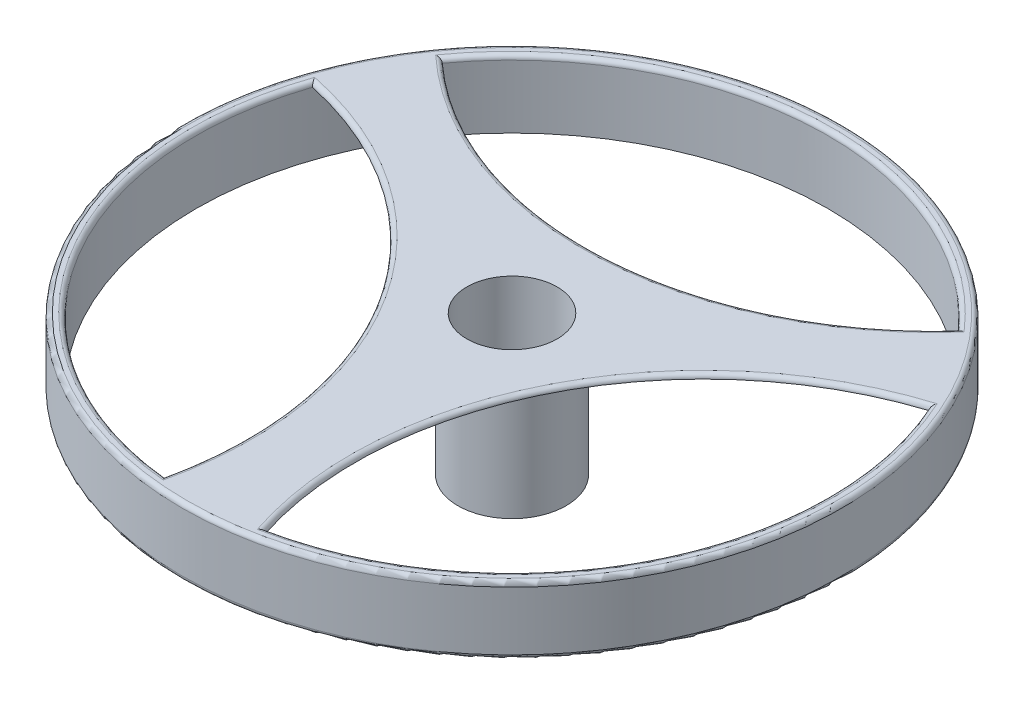
SolidWorks part; units mm, degrees
ref_plane "Front Plane" through (0, 0, 0) normal (0, 0, 1) x (1, 0, 0)
ref_plane "Top Plane" through (0, 0, 0) normal (0, 1, 0) x (1, 0, 0)
ref_plane "Right Plane" through (0, 0, 0) normal (1, 0, 0) x (0, 0, -1)
sketch "Sketch1" plane through (0, 0, 0) normal (0, 1, 0) x (1, 0, 0)
  circle A0 centre (0, 0) radius 7.3
  dimension "D1" = 14.6
extrude "Boss-Extrude1" add sketch "Sketch1" along normal blind 1.5
sketch "Sketch2" plane through (0, 1.5, 0) normal (0, 1, 0) x (1, 0, 0)
  circle A0 centre (0, 0) radius 1.1836 construction
  arc A1 (1.3984, -6.8589) -> (6.3958, 2.845) centre (0, 0) ccw
  arc A2 (1.3984, -6.8589) -> (6.3958, 2.845) centre (8.749, -4.5056) cw
  dimension "D1" = 14
extrude "Cut-Extrude1" cut sketch "Sketch2" against normal blind 1.5
pattern_circular "CirPattern1" count 3 over 360 about axis through (0, 1.5, 0) along (0, -1, 0) of "Cut-Extrude1"
sketch "Sketch3" plane through (0, 1.5, 0) normal (0, 1, 0) x (1, 0, 0)
  circle A0 centre (0, 0) radius 1
  dimension "D1" = 2
extrude "Cut-Extrude2" cut sketch "Sketch3" against normal blind 1.5
sketch "Sketch4" plane through (0, 0, 0) normal (0, -1, 0) x (1, 0, 0)
  circle A0 centre (0, 0) radius 7
extrude "Cut-Extrude3" cut sketch "Sketch4" against normal blind 1.4
sketch "Sketch5" plane through (0, 1.4, 0) normal (0, -1, 0) x (1, 0, 0)
  circle A0 centre (0, 0) radius 1.2
  circle A1 centre (0, 0) radius 1
  dimension "D1" = 2.4
extrude "Boss-Extrude2" add sketch "Sketch5" along normal blind 3
fillet "Fillet1" radius 0.1 8 edges at (-5.8871, 1.5, 3.7871) (-1.7854, 1.5, 1.1485) (6.2232, 1.5, 3.2049) (-0.3361, 1.5, -6.9919) (1.8873, 1.5, 0.972) (-0.1019, 1.5, -2.1205) (0, 0, 7.3) (0, 1.5, 7.3)
